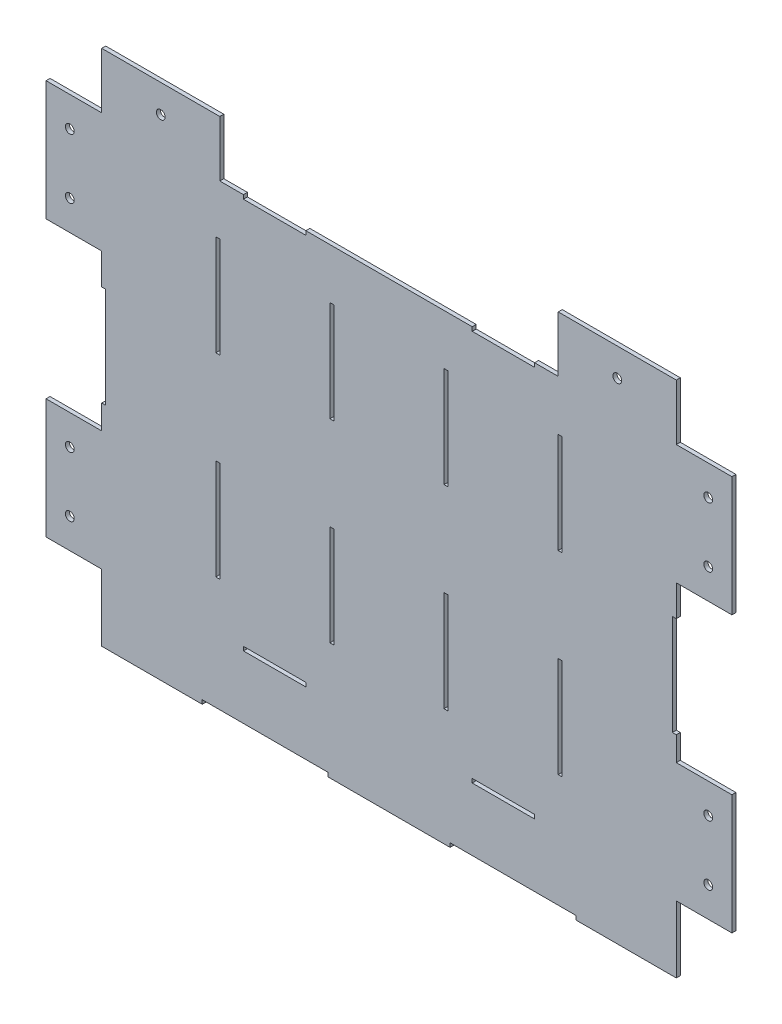
SolidWorks part; units mm, degrees
material "6061-T6 (SS)"
ref_plane "X-Y Datum" through (0, 0, 0) normal (0, 0, 1) x (1, 0, 0)
ref_plane "X-Z Datum" through (0, 0, 0) normal (0, 1, 0) x (1, 0, 0)
ref_plane "Y-Z Datum" through (0, 0, 0) normal (1, 0, 0) x (0, 0, -1)
sketch "Sketch1" plane through (0, 0, 0) normal (0, 0, 1) x (1, 0, 0)
  line L0 (-228.6115, 0) -> (228.6115, 0) construction
  line L1 (-228.6115, -157.216) -> (228.6115, -157.216)
  line L2 (-228.6115, -157.216) -> (-228.6115, 157.216)
  line L3 (-228.6115, 157.216) -> (228.6115, 157.216)
  line L4 (228.6115, -157.216) -> (228.6115, 157.216)
  line L5 (-228.6115, -157.216) -> (228.6115, 157.216) construction
  line L6 (-228.6115, 157.216) -> (228.6115, -157.216) construction
  line L8 (-228.6115, 0) -> (-134.6215, 0) construction
  line L9 (-225.4325, -154.041) -> (-225.4325, 154.041)
  line L10 (-224.4165, -153.025) -> (-138.8165, -153.025) construction
  line L15 (-224.4165, -153.025) -> (-224.4165, 153.025) construction
  line L16 (-224.4165, 153.025) -> (-138.8165, 153.025) construction
  line L17 (-138.8165, -153.025) -> (-138.8165, 153.025) construction
  line L18 (-224.4165, -153.025) -> (-138.8165, 153.025) construction
  line L19 (-224.4165, 153.025) -> (-138.8165, -153.025) construction
  line L20 (-225.4325, 154.041) -> (-137.8005, 154.041)
  line L21 (-137.8005, -154.041) -> (-137.8005, 154.041)
  line L22 (-225.4325, -154.041) -> (-137.8005, -154.041)
  line L26 (-134.6255, 154.041) -> (-46.9935, 154.041)
  line L27 (-133.6095, -153.025) -> (-48.0095, -153.025) construction
  line L28 (-133.6095, -153.025) -> (-133.6095, 153.025) construction
  line L29 (-133.6095, 153.025) -> (-48.0095, 153.025) construction
  line L30 (-48.0095, -153.025) -> (-48.0095, 153.025) construction
  line L31 (-133.6095, -153.025) -> (-48.0095, 153.025) construction
  line L32 (-133.6095, 153.025) -> (-48.0095, -153.025) construction
  line L33 (-46.9935, -154.041) -> (-46.9935, 154.041)
  line L34 (-134.6255, -154.041) -> (-46.9935, -154.041)
  line L35 (-134.6255, -154.041) -> (-134.6255, 154.041)
  line L36 (42.7975, -153.025) -> (42.7975, 153.025) construction
  line L37 (43.8135, -154.041) -> (43.8135, 154.041)
  line L38 (-42.8025, -153.025) -> (42.7975, 153.025) construction
  line L39 (-42.8025, 153.025) -> (42.7975, -153.025) construction
  line L40 (-42.8025, -153.025) -> (-42.8025, 153.025) construction
  line L41 (-43.8185, -154.041) -> (-43.8185, 154.041)
  line L42 (-42.8025, 153.025) -> (42.7975, 153.025) construction
  line L43 (-43.8185, 154.041) -> (43.8135, 154.041)
  line L44 (-42.8025, -153.025) -> (42.7975, -153.025) construction
  line L45 (-43.8185, -154.041) -> (43.8135, -154.041)
  line L46 (133.6045, -153.025) -> (133.6045, 153.025) construction
  line L47 (134.6205, -154.041) -> (134.6205, 154.041)
  line L48 (48.0045, -153.025) -> (133.6045, 153.025) construction
  line L49 (48.0045, 153.025) -> (133.6045, -153.025) construction
  line L50 (48.0045, -153.025) -> (48.0045, 153.025) construction
  line L51 (46.9885, -154.041) -> (46.9885, 154.041)
  line L52 (48.0045, 153.025) -> (133.6045, 153.025) construction
  line L53 (46.9885, 154.041) -> (134.6205, 154.041)
  line L54 (48.0045, -153.025) -> (133.6045, -153.025) construction
  line L55 (46.9885, -154.041) -> (134.6205, -154.041)
  line L56 (224.4115, -153.025) -> (224.4115, 153.025) construction
  line L57 (225.4275, -154.041) -> (225.4275, 154.041)
  line L58 (138.8115, -153.025) -> (224.4115, 153.025) construction
  line L59 (138.8115, 153.025) -> (224.4115, -153.025) construction
  line L60 (138.8115, -153.025) -> (138.8115, 153.025) construction
  line L61 (137.7955, -154.041) -> (137.7955, 154.041)
  line L62 (138.8115, 153.025) -> (224.4115, 153.025) construction
  line L63 (137.7955, 154.041) -> (225.4275, 154.041)
  line L64 (138.8115, -153.025) -> (224.4115, -153.025) construction
  line L65 (137.7955, -154.041) -> (225.4275, -154.041)
  line L67 (-228.6115, -157.216) -> (225.4365, -157.216)
  line L71 (-228.6115, -157.216) -> (228.6115, -157.216)
  line L74 (-225.4365, -157.216) -> (225.4365, -157.216)
  line L75 (-225.4365, -157.216) -> (-225.4365, -208.106)
  line L76 (-225.4365, -208.106) -> (225.4365, -208.106)
  line L77 (225.4365, -157.216) -> (225.4365, -208.106)
  line L79 (-228.6115, -157.216) -> (228.6115, -157.216)
  line L80 (-228.6115, -157.216) -> (-228.6115, -210.392)
  line L81 (-228.6115, -210.392) -> (228.6115, -210.392)
  line L82 (228.6115, -157.216) -> (228.6115, -210.392)
  point P0 (0, 0)
  point P10 (-181.6165, 0)
  point P22 (-90.8095, 0)
  dimension "D1" = 314.432
  dimension "D2" = 457.223
  dimension "D4" = 1.016
  dimension "D5" = 3.179
  dimension "D6" = 3.175
  dimension "D7" = 1.016
  dimension "D8" = 90.807
  dimension "D9" = 3.175
  dimension "D11" = 3.175
  dimension "D12" = 50.89
  dimension "D13" = 2.286
  dimension "D14" = 3.175
  dimension "D15" = 3.175
  dimension "D10" = 4
extrude "Boss-Extrude2" add sketch "Sketch1" along normal blind 3.175 contours L61 L65 L57 L63 | L51 L55 L47 L53 | L41 L45 L37 L43 | L35 L34 L33 L26 | L9 L22 L21 L20 | L1 L71 L4 L3 L2 L65 L61 L63 L57 L55 L51 L53 L47 L45 L41 L43 L37 L22 L9 L20 L21 L34 L35 L26 L33 | L77 L71 L75 L76 | L82 L1 L77 L76 L75 L80 L81 region at (-228.0566, 0, 0) region at (-227.024, -161.819, 0) region at (0, -182.661, 0) region at (-181.6165, 0, 0) region at (-90.8095, 0, 0) region at (-0.0025, 0, 0) region at (90.8045, 0, 0) region at (181.6115, 0, 0)
sketch "Sketch4" plane through (0, 0, 3.175) normal (0, 0, 1) x (1, 0, 0)
  line L0 (-136.213, 117.216) -> (-136.213, 157.216) construction
  line L1 (-228.6115, 157.216) -> (228.6115, 157.216) construction
  line L2 (-228.6115, 157.216) -> (228.6115, 157.216) construction
  line L5 (-134.6255, -154.041) -> (-134.6255, 154.041) construction
  line L6 (-137.8005, 37.216) -> (-134.6255, 37.216)
  line L7 (-137.8005, 37.216) -> (-137.8005, 117.216)
  line L8 (-137.8005, 117.216) -> (-134.6255, 117.216)
  line L9 (-134.6255, 37.216) -> (-134.6255, 117.216)
  line L10 (-137.8005, 37.216) -> (-134.6255, 117.216) construction
  line L11 (-137.8005, 117.216) -> (-134.6255, 37.216) construction
  line L13 (-45.406, 153.025) -> (-45.406, -157.216) construction
  line L14 (-228.6115, -157.216) -> (228.6115, -157.216) construction
  dimension "D1" = 40
  dimension "D2" = 3.175
  dimension "D3" = 80
  dimension "D4" = 90.807
extrude "Cut-Extrude1" cut sketch "Sketch4" against normal blind 3.175 contours L6 L9 L8 L7 region at (-136.213, 77.216, 3.175)
mirror "Mirror1" about plane through (0, 0, 0) normal (0, 1, 0) of "Cut-Extrude1"
pattern_linear "LPattern1" count 4 spacing 90.807 along (1, 0, 0) of "Mirror1"
sketch "Sketch5" plane through (0, 0, 3.175) normal (0, 0, 1) x (1, 0, 0)
  line L0 (-225.4365, -157.216) -> (-228.6115, -157.216)
  line L1 (-225.4325, -154.041) -> (-228.6115, -154.041)
  line L2 (-228.6115, -157.216) -> (-228.6115, 157.216) construction
  line L3 (-228.6115, -154.041) -> (-228.6115, -157.216)
  line L4 (-228.6115, -155.6285) -> (-194.996, -155.6285)
  line L5 (-194.996, -155.6285) -> (-91.0201, -155.6285) construction
  line L6 (-225.4325, -154.041) -> (-137.8005, -154.041) construction
  line L7 (-115.8495, -157.216) -> (-66.1907, -157.216)
  line L8 (-115.8495, -157.216) -> (-115.8495, -154.041)
  line L9 (-115.8495, -154.041) -> (-66.1907, -154.041)
  line L10 (-66.1907, -157.216) -> (-66.1907, -154.041)
  line L11 (-115.8495, -157.216) -> (-66.1907, -154.041) construction
  line L12 (-115.8495, -154.041) -> (-66.1907, -157.216) construction
  dimension "D1" = 112.762
  dimension "D2" = 49.6588
extrude "Cut-Extrude2" cut sketch "Sketch5" against normal blind 3.175 contours L7 L10 L9 L8 region at (-91.0201, -155.6285, 3.175)
mirror "Mirror2" about plane through (0, 0, 0) normal (1, 0, 0) of "Cut-Extrude2"
mirror "Mirror3" about plane through (0, 0, 0) normal (0, 1, 0) of "Mirror2"
sketch "Sketch6" plane through (0, 0, 3.175) normal (0, 0, 1) x (1, 0, 0)
  line L0 (-228.6115, -210.392) -> (-228.6115, 157.216) construction
  line L3 (-228.6115, 157.216) -> (-115.8495, 157.216) construction
  line L5 (-225.4365, 157.216) -> (-228.6115, 157.216)
  line L6 (-227.024, 157.216) -> (-227.024, 37.216) construction
  line L7 (-227.024, 37.216) -> (-227.024, -42.784) construction
  line L9 (-225.4365, -42.784) -> (-228.6115, -42.784)
  line L10 (-225.4365, -42.784) -> (-225.4365, 37.216)
  line L11 (-225.4365, 37.216) -> (-228.6115, 37.216)
  line L12 (-228.6115, -42.784) -> (-228.6115, 37.216)
  line L13 (-225.4365, -42.784) -> (-228.6115, 37.216) construction
  line L14 (-225.4365, 37.216) -> (-228.6115, -42.784) construction
  point P11 (-227.024, -2.784)
  dimension "D1" = 3.175
  dimension "D2" = 120
  dimension "D3" = 80
extrude "Cut-Extrude3" cut sketch "Sketch6" against normal through all contours L12 L9 L10 L11 region at (-227.024, -2.784, 3.175)
mirror "Mirror5" about plane through (0, 0, 0) normal (1, 0, 0) of "Cut-Extrude3"
sketch "Sketch7" plane through (0, 0, 3.175) normal (0, 0, 1) x (1, 0, 0)
  line L1 (-228.6115, -210.392) -> (-228.6115, -42.784) construction
  line L5 (-148.6115, -210.392) -> (-48.6115, -210.392)
  line L6 (-148.6115, -210.392) -> (-148.6115, -207.217)
  line L7 (-148.6115, -207.217) -> (-48.6115, -207.217)
  line L8 (-48.6115, -210.392) -> (-48.6115, -207.217)
  line L9 (-148.6115, -210.392) -> (-48.6115, -207.217) construction
  line L10 (-148.6115, -207.217) -> (-48.6115, -210.392) construction
  point P7 (-98.6115, -208.8045)
  dimension "D1" = 80
  dimension "D2" = 100
  dimension "D3" = 3.175
extrude "Cut-Extrude4" cut sketch "Sketch7" against normal blind 3.175 contours L5 L8 L7 L6 region at (-98.6115, -208.8045, 3.175)
mirror "Mirror6" about plane through (0, 0, 0) normal (1, 0, 0) of "Cut-Extrude4"
sketch "Sketch8" plane through (0, 0, 0) normal (0, 0, -1) x (-1, 0, 0)
  line L0 (-228.6115, -210.392) -> (-228.6115, -42.784) construction
  line L1 (-228.6115, 157.216) -> (-279.4115, 157.216)
  line L2 (-228.6115, 157.216) -> (-228.6115, 61.966)
  line L3 (-228.6115, 61.966) -> (-279.4115, 61.966)
  line L4 (-279.4115, 157.216) -> (-279.4115, 61.966)
  line L5 (-228.6115, -157.2452) -> (-279.4115, -157.2452)
  line L6 (-228.6115, -157.2452) -> (-228.6115, -61.9952)
  line L7 (-228.6115, -61.9952) -> (-279.4115, -61.9952)
  line L8 (-279.4115, -157.2452) -> (-279.4115, -61.9952)
  line L9 (-254.0115, 157.216) -> (-254.0115, 61.966) construction
  line L10 (-254.0115, -85.8077) -> (-254.0115, -133.4327) construction
  line L11 (-279.4115, 109.591) -> (-228.6115, 109.591) construction
  line L12 (-254.0115, 157.216) -> (-254.0115, 109.591) construction
  line L13 (-272.8865, 157.216) -> (-272.8865, 61.966)
  line L14 (-148.6115, -210.392) -> (-228.6115, -210.392) construction
  line L15 (-228.6115, -109.6202) -> (-279.4115, -109.6202) construction
  line L16 (-181.6215, 201.666) -> (-181.6215, 157.216) construction
  line L17 (-228.6115, 157.216) -> (-134.6315, 157.216)
  line L18 (-228.6115, 157.216) -> (-228.6115, 201.666)
  line L19 (-228.6115, 201.666) -> (-134.6315, 201.666)
  line L20 (-134.6315, 157.216) -> (-134.6315, 201.666)
  line L22 (-115.8495, 157.216) -> (-228.6115, 157.216) construction
  line L23 (-272.8865, -61.9952) -> (-272.8865, -157.2452)
  circle A1 centre (-254.0115, 133.4035) radius 3
  circle A2 centre (-254.0115, 85.7785) radius 3
  circle A3 centre (-254.0115, -85.8077) radius 3
  circle A4 centre (-254.0115, -133.4327) radius 3
  circle A5 centre (-181.6215, 179.441) radius 3
  point P13 (-254.0115, -109.6202)
  point P44 (-257.0115, 133.4035)
  point P45 (-254.0115, -136.4327)
  point P46 (-254.0115, -157.2452)
  dimension "D1" = 95.25
  dimension "D2" = 15.875
  dimension "D4" = 47.625
  dimension "D5" = 6
  dimension "D7" = 93.98
  dimension "D8" = 53.1468
  dimension "D14" = 6
  dimension "D3" = 25.4
  dimension "D6" = 22.225
extrude "Boss-Extrude3" add sketch "Sketch8" against normal blind 3.175 contours L1 L4 L3 L2 A1 A2 | L17 L20 L19 L18 | L8 L5 L6 L7 A3 A4 region at (250.7047, 109.591, 0) region at (227.5719, 179.441, 0) region at (250.7047, -109.6202, 0)
mirror "Mirror7" about plane through (0, 0, 0) normal (1, 0, 0) of "Boss-Extrude3"
hole_wizard "M6 Clearance Hole1" positions "Sketch11" profile "Sketch10" hole size "M6" standard "ANSI Metric" end condition through all
sketch "Sketch11" plane through (0, 0, 0) normal (0, 0, -1) x (-1, 0, 0)
  point P0 (-254.0115, 133.4035)
  point P3 (-254.0115, 85.7785)
  point P6 (-254.0115, -85.8077)
  point P9 (-254.0115, -133.4327)
  point P12 (-181.6215, 179.441)
  point P15 (181.6215, 179.441)
  point P18 (254.0115, 133.4035)
  point P21 (254.0115, 85.7785)
  point P24 (254.0115, -85.8077)
  point P27 (254.0115, -133.4327)
sketch "Sketch10" plane through (254.0115, 133.4035, 0) normal (1, 0, 0) x (0, 1, 0)
  line L0 (0, 0) -> (0, 3.175)
  line L1 (0, 3.175) -> (3.5, 3.175)
  line L2 (3.5, 3.175) -> (3.5, 0)
  line L5 (3.5, 0) -> (0, 0)
  line L11 (0, -6.35) -> (0, 107.95) construction
  dimension "Thru Hole Dia." = 7
  dimension "Thru Hole Depth" = 3.175
